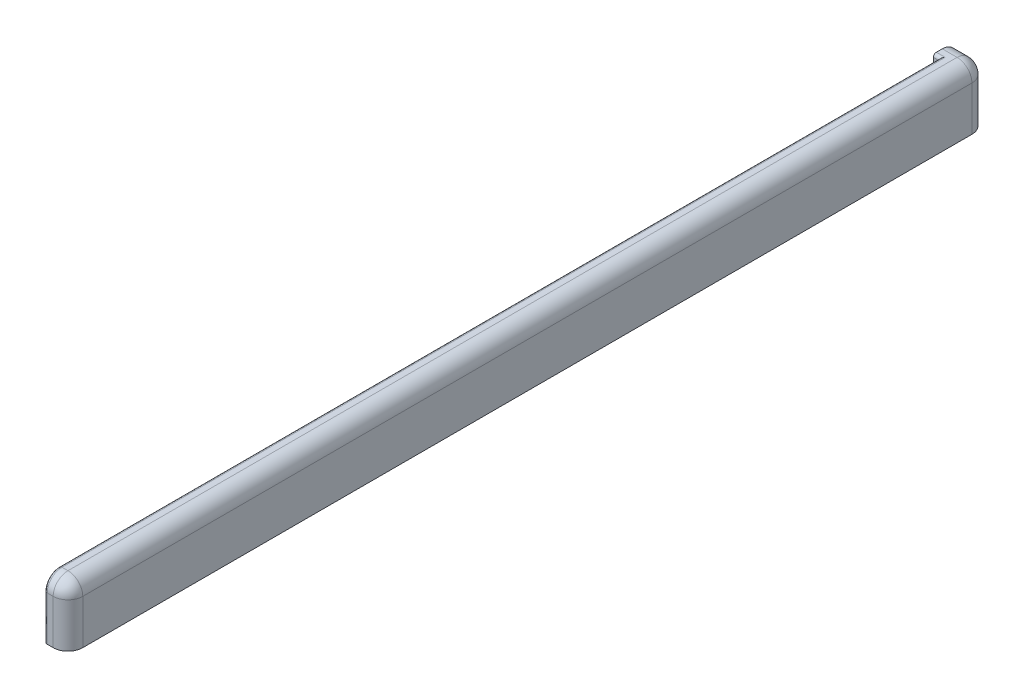
SolidWorks part; units mm, degrees
ref_plane "Front Plane" through (0, 0, 0) normal (0, 0, 1) x (1, 0, 0)
ref_plane "Top Plane" through (0, 0, 0) normal (0, 1, 0) x (1, 0, 0)
ref_plane "Right Plane" through (0, 0, 0) normal (1, 0, 0) x (0, 0, -1)
sketch "Sketch1" plane through (0, 0, 0) normal (0, 1, 0) x (1, 0, 0)
  line L1 (-19.5, 77.5) -> (19.5, 77.5)
  line L2 (-19.5, 77.5) -> (-19.5, -77.5)
  line L3 (-19.5, -77.5) -> (19.5, -77.5)
  line L4 (19.5, 77.5) -> (19.5, -77.5)
  line L5 (-19.5, 77.5) -> (19.5, -77.5) construction
  line L6 (-19.5, -77.5) -> (19.5, 77.5) construction
  point P0 (0, 0)
  dimension "D1" = 39
  dimension "D2" = 155
extrude "Boss-Extrude1" add sketch "Sketch1" along normal blind 2
sketch "Sketch2" plane through (0, 2, 0) normal (0, 1, 0) x (1, 0, 0)
  line L0 (-17.5, -75.5) -> (-17.5, -77.5)
  line L1 (-19.5, 77.5) -> (19.5, 77.5)
  line L2 (-19.5, 77.5) -> (-19.5, -77.5)
  line L3 (-19.5, -77.5) -> (19.5, -77.5)
  line L4 (19.5, 77.5) -> (19.5, -77.5)
  line L5 (-17.5, 75.5) -> (17.5, 75.5)
  line L6 (-17.5, 75.5) -> (-17.5, -75.5)
  line L7 (-17.5, -75.5) -> (17.5, -75.5)
  line L8 (17.5, 75.5) -> (17.5, -75.5)
  line L9 (-17.5, 75.5) -> (17.5, -75.5) construction
  line L10 (-17.5, -75.5) -> (17.5, 75.5) construction
  line L11 (17.5, -75.5) -> (17.5, -77.5)
  point P6 (0, 0)
  line M9 (19.5, -77.5) -> (19.5, 77.5)
  line M10 (19.5, 77.5) -> (-19.5, 77.5)
  line M11 (-19.5, 77.5) -> (-19.5, -77.5)
  line M12 (-19.5, -77.5) -> (19.5, -77.5)
  dimension "D1" = 2
  dimension "D2" = 2
extrude "Boss-Extrude2" add sketch "Sketch2" along normal blind 38 contours L8 L11 L3 L0 L6 L5 M9 M10 M11 M12 region at (-19.0983, 2, 76.5)
sketch "Sketch3" plane through (0, 2, 0) normal (0, 1, 0) x (1, 0, 0)
  line L0 (-17.5, 75.5) -> (-17.5, -77.5) construction
  line L1 (-17.5, -77.5) -> (-15.5, -77.5)
  line L2 (-17.5, -77.5) -> (-17.5, -75.5)
  line L3 (-17.5, -75.5) -> (-15.5, -75.5)
  line L4 (-15.5, -77.5) -> (-15.5, -75.5)
  line L5 (-17.5, -73.3) -> (-15.5, -73.3)
  line L6 (-17.5, -73.3) -> (-17.5, -71.3)
  line L7 (-17.5, -71.3) -> (-15.5, -71.3)
  line L8 (-15.5, -73.3) -> (-15.5, -71.3)
  line L9 (17.5, 75.5) -> (17.5, -77.5) construction
  line L10 (17.5, -77.5) -> (15.5, -77.5)
  line L11 (17.5, -77.5) -> (17.5, -75.5)
  line L12 (17.5, -75.5) -> (15.5, -75.5)
  line L13 (15.5, -77.5) -> (15.5, -75.5)
  line L14 (17.5, -73.3) -> (15.5, -73.3)
  line L15 (17.5, -73.3) -> (17.5, -71.3)
  line L16 (17.5, -71.3) -> (15.5, -71.3)
  line L17 (15.5, -73.3) -> (15.5, -71.3)
  line L18 (15.5, -75.5) -> (15.5, -73.3) construction
  line L19 (-15.5, -73.3) -> (15.5, -73.3) construction
  line L20 (-15.5, -75.5) -> (-15.5, -73.3) construction
  line L21 (-15.5, -75.5) -> (15.5, -75.5) construction
  line L22 (15.5, -71.3) -> (-15.5, -71.3) construction
  dimension "D1" = 2
  dimension "D2" = 2
  dimension "D3" = 2.2
  dimension "D4" = 2
extrude "Boss-Extrude3" add sketch "Sketch3" along normal up to surface (38 mm away) up to face at (0, 40, 0.5)
sketch "Sketch4" plane through (0, 0, -75.5) normal (0, 0, 1) x (1, 0, 0)
  line L0 (-17.5, 40) -> (-15.5, 40)
  line L1 (-17.5, 40) -> (17.5, 40) construction
  line L2 (-15.5, 40) -> (-15.5, 38)
  line L3 (-15.5, 38) -> (-17.5, 38)
  line L5 (-17.5, 38) -> (-17.5, 40)
  line L7 (-17.5, 40) -> (-17.5, 2) construction
  line L8 (-15.5, 33.8) -> (-17.5, 31.8)
  line L9 (-17.5, 31.8) -> (-17.5, 35.8)
  line L10 (-15.5, 33.8) -> (-15.5, 35.8)
  line L11 (-15.5, 35.8) -> (-17.5, 35.8)
  line L12 (0, 0) -> (0, 40) construction
  line L13 (15.5, 35.8) -> (17.5, 35.8)
  line L14 (15.5, 33.8) -> (15.5, 35.8)
  line L15 (17.5, 31.8) -> (17.5, 35.8)
  line L16 (15.5, 33.8) -> (17.5, 31.8)
  line L17 (17.5, 38) -> (17.5, 40)
  line L18 (15.5, 38) -> (17.5, 38)
  line L19 (15.5, 40) -> (15.5, 38)
  line L20 (17.5, 40) -> (15.5, 40)
  dimension "D1" = 2
  dimension "D2" = 2
  dimension "D3" = 45
  dimension "D4" = 2.2
  dimension "D5" = 2
extrude "Boss-Extrude4" add sketch "Sketch4" along normal up to surface (153 mm away) up to face at (0, 20.5, 77.5)
sketch "Sketch5" plane through (0, 2, 0) normal (0, 1, 0) x (1, 0, 0)
  line L1 (-15.5, -77.5) -> (15.5, -77.5)
  line L2 (-15.5, -77.5) -> (-15.5, -75.5)
  line L3 (-15.5, -75.5) -> (15.5, -75.5)
  line L4 (15.5, -77.5) -> (15.5, -75.5)
  line L5 (-15.5, -71.3) -> (15.5, -71.3)
  line L6 (-15.5, -71.3) -> (-15.5, -73.3)
  line L7 (-15.5, -73.3) -> (15.5, -73.3)
  line L8 (15.5, -71.3) -> (15.5, -73.3)
sketch "Sketch6" plane through (0, 0, -75.5) normal (0, 0, 1) x (1, 0, 0)
  line L0 (-17.5, 38) -> (-15.5, 38) construction
  line L1 (-17.5, 38) -> (17.5, 38)
  line L2 (-17.5, 38) -> (-17.5, 35.8)
  line L3 (-17.5, 35.8) -> (17.5, 35.8)
  line L4 (17.5, 38) -> (17.5, 35.8)
  line L5 (-17.5, 38) -> (-17.5, 35.8) construction
  line L6 (-15.5, 35.8) -> (-17.5, 35.8) construction
extrude "Cut-Extrude1" cut sketch "Sketch6" along normal through all
sketch "Sketch7" plane through (0, 2, 0) normal (0, 1, 0) x (1, 0, 0)
  line L1 (-17.5, -75.5) -> (17.5, -75.5)
  line L2 (-17.5, -75.5) -> (-17.5, -73.3)
  line L3 (-17.5, -73.3) -> (17.5, -73.3)
  line L4 (17.5, -75.5) -> (17.5, -73.3)
extrude "Cut-Extrude2" cut sketch "Sketch7" along normal through all
extrude "Boss-Extrude5" add sketch "Sketch5" along normal blind 2
sketch "Sketch8" plane through (0, 0, 0) normal (1, 0, 0) x (0, 0, -1)
  line L0 (75.5, 40) -> (73.5, 40)
  line L1 (-73.3, 40) -> (75.5, 40) construction
  line L2 (73.5, 40) -> (73.5, 38)
  line L3 (-73.3, 38) -> (75.5, 38) construction
  line L4 (73.5, 38) -> (75.5, 38)
  line L5 (75.5, 38) -> (75.5, 40)
  line L6 (75.5, 35.8) -> (73.5, 35.8)
  line L7 (-73.3, 35.8) -> (75.5, 35.8) construction
  line L8 (73.5, 35.8) -> (73.5, 33.8)
  line L9 (-71.3, 33.8) -> (75.5, 33.8) construction
  line L10 (73.5, 33.8) -> (75.5, 31.8)
  line L11 (75.5, 31.8) -> (75.5, 35.8)
  dimension "D1" = 2
extrude "Boss-Extrude6" add sketch "Sketch8" along normal up to surface and the other way up to surface up to face at (17.5, 16.9, -2.1) other way up to face at (-17.5, 16.9, -2.1)
sketch "Sketch10" plane through (-17.5, 0, 0) normal (1, 0, 0) x (0, 0, -1)
  line L1 (-75.5, 35.8) -> (-77.5, 35.8)
  line L2 (-75.5, 35.8) -> (-75.5, 38)
  line L3 (-75.5, 38) -> (-77.5, 38)
  line L4 (-77.5, 35.8) -> (-77.5, 38)
  line L5 (-73.3, 40) -> (-75.5, 40)
  line L6 (-73.3, 40) -> (-73.3, 38)
  line L7 (-73.3, 38) -> (-75.5, 38)
  line L8 (-75.5, 40) -> (-75.5, 38)
  line M1 (-75.5, 40) -> (-75.5, 38)
  line M2 (-75.5, 38) -> (-77.5, 38)
  line M3 (-77.5, 38) -> (-77.5, 35.8)
  line M4 (-77.5, 35.8) -> (-75.5, 35.8)
  line M11 (-73.3, 38) -> (-73.3, 40)
  line M12 (-73.3, 40) -> (-75.5, 40)
extrude "Boss-Extrude8" add sketch "Sketch10" along normal up to surface (2 mm away) contours L2 M4 M2 M3 | L7 M11 M12 M1 region at (-17.5, 39, 74.4) region at (-17.5, 36.9, 76.5) up to face at (-15.5, 39, -0.1)
sketch "Sketch11" plane through (17.5, 0, 0) normal (-1, 0, 0) x (0, 0, 1)
  line L1 (75.5, 35.8) -> (77.5, 35.8)
  line L2 (75.5, 35.8) -> (75.5, 38)
  line L3 (75.5, 38) -> (77.5, 38)
  line L4 (77.5, 35.8) -> (77.5, 38)
  line L5 (73.3, 40) -> (75.5, 40)
  line L6 (73.3, 40) -> (73.3, 38)
  line L7 (73.3, 38) -> (75.5, 38)
  line L8 (75.5, 40) -> (75.5, 38)
  line M2 (75.5, 35.8) -> (77.5, 35.8)
  line M3 (77.5, 35.8) -> (77.5, 38)
  line M4 (77.5, 38) -> (75.5, 38)
  line M5 (75.5, 38) -> (75.5, 40)
  line M6 (75.5, 40) -> (73.3, 40)
  line M7 (73.3, 40) -> (73.3, 38)
extrude "Boss-Extrude9" add sketch "Sketch11" along normal up to surface (2 mm away) contours L2 M2 M3 M4 | L7 M7 M5 M6 region at (17.5, 36.9, 76.5) region at (17.5, 39, 74.4) up to face at (15.5, 39, 76.5)
fillet "Fillet2" radius 2.5 17 edges at (-17.5, 16.9, 71.3) (17.5, 16.9, 71.3) (19.5, 20, 77.5) (-19.5, 20, 77.5) (-19.5, 20, -77.5) (-17.5, 16.9, -75.5) (17.5, 16.9, -75.5) (19.5, 20, -77.5) (-19.5, 40, 0) (0, 40, -77.5) (19.5, 40, 0) (0, 0, -77.5) (0, 0, 77.5) (-19.5, 0, 0) (19.5, 0, 0) (-17.5, 40, 77.5) (17.5, 40, 77.5)
sketch "Sketch13" plane through (0, 0, -77.5) normal (0, 0, -1) x (-1, 0, 0)
  line L0 (15.5, 37.5) -> (15.5, 4) construction
  line L1 (-15.5, 7) -> (15.5, 7)
  line L2 (-15.5, 7) -> (-15.5, 4)
  line L3 (-15.5, 4) -> (15.5, 4)
  line L4 (15.5, 7) -> (15.5, 4)
  dimension "D1" = 3
sketch "Sketch14" plane through (0, 0, -75.5) normal (0, 0, 1) x (1, 0, 0)
  line L1 (-18.25, 9) -> (18.25, 9)
  line L2 (-18.25, 9) -> (-18.25, 1.25)
  line L3 (-18.25, 1.25) -> (18.25, 1.25)
  line L4 (18.25, 9) -> (18.25, 1.25)
  line L5 (15.5, 7) -> (-15.5, 7) construction
  line L7 (17, 0) -> (17, 2.5) construction
  line L8 (19.5, 2.5) -> (17, 2.5) construction
  line L10 (-19.5, 2.5) -> (-17, 2.5) construction
  point P20 (17, 1.25)
  point P23 (18.25, 2.5)
  point P26 (-18.25, 2.5)
  dimension "D1" = 2
extrude "Boss-Extrude10" add sketch "Sketch14" along normal blind 2
extrude "Cut-Extrude4" cut sketch "Sketch13" against normal blind 2
fillet "Fillet3" radius 2 1 edges at (0, 9, -73.5)
fillet "Fillet4" radius 0.5 12 edges at (0, 4, -77.5) (0, 7, -77.5) (15.5, 7, -76.5) (15.5, 4, -76.5) (15.5, 5.5, -77.5) (-15.5, 4, -76.5) (-15.5, 7, -76.5) (-15.5, 5.5, -77.5) (0, 7, -75.5) (-15.5, 5.5, -75.5) (0, 4, -75.5) (15.5, 5.5, -75.5)
sketch "Sketch15" plane through (0, 0, 0) normal (0, -1, 0) x (1, 0, 0)
  line L0 (0, 77.5) -> (0, 0) construction
  line L1 (-17, 77.5) -> (17, 77.5) construction
  line L2 (0, 0) -> (0, -77.5) construction
  line L4 (17, -77.5) -> (-17, -77.5) construction
  circle A0 centre (0, 38.75) radius 5.1
  circle A1 centre (0, -38.75) radius 5.1
  dimension "D1" = 10.2
extrude "Cut-Extrude5" cut sketch "Sketch15" against normal through all
sketch "Sketch16" plane through (0, 2, 0) normal (0, 1, 0) x (1, 0, 0)
  circle A0 centre (0, 38.75) radius 7.1
  circle A1 centre (0, -38.75) radius 7.1
  circle A2 centre (0, 38.75) radius 5.1 construction
  dimension "D1" = 2
extrude "Boss-Extrude11" add sketch "Sketch16" along normal blind 1
fillet "Fillet5" radius 0.5 4 edges at (0, 2, 45.85) (0, 2, -31.65) (0, 3, 45.85) (0, 3, -31.65)
sketch "Sketch12" plane through (0, 0, -75.5) normal (0, 0, 1) x (1, 0, 0)
  line L0 (0, 0) -> (0, 40) construction
  line L1 (15.5, 40) -> (-15.5, 40) construction
  line L2 (0, 20) -> (-10, 20)
  line L3 (0, 20) -> (-9.0097, 15.6612)
  line L4 (0, 20) -> (-6.2349, 12.1817)
  line L5 (0, 20) -> (-2.2252, 10.2507)
  line L6 (0, 20) -> (2.2252, 10.2507)
  line L7 (0, 20) -> (6.2349, 12.1817)
  line L8 (0, 20) -> (9.0097, 15.6612)
  line L9 (0, 20) -> (10, 20)
  line L10 (0, 20) -> (9.0097, 24.3388)
  line L11 (0, 20) -> (6.2349, 27.8183)
  line L12 (0, 20) -> (2.2252, 29.7493)
  line L13 (0, 20) -> (-2.2252, 29.7493)
  line L14 (0, 20) -> (-6.2349, 27.8183)
  line L15 (0, 20) -> (-9.0097, 24.3388)
  circle A0 centre (0, 20) radius 10
  circle A1 centre (0, 20) radius 7.5
  circle A2 centre (0, 20) radius 5
  circle A3 centre (0, 20) radius 2.5
  point P26 (0, 20)
  dimension "D1" = 20
  dimension "D2" = 2.5
  dimension "D3" = 2.5
  dimension "D4" = 2.5
  dimension "D5" = 14
extrude "Cut-Extrude3" cut sketch "Sketch12" against normal through all contours A1 L6 A0 L7 | A1 L4 A0 L5 | A1 L2 A0 L3 | A1 L14 A0 L15 | A1 L0 A0 L13 | L0 A1 L12 A0 | A1 L10 A0 L11 | A1 L8 A0 L9 | A3 L8 A2 L9 | A3 L10 A2 L11 | L0 A3 L12 A2 | A3 L0 A2 L13 | A3 L14 A2 L15 | A3 L2 A2 L3 | A3 L4 A2 L5 | A3 L6 A2 L7 region at (-3.7903, 12.1293, -75.5) region at (3.7903, 12.1293, -75.5) region at (-1.6732, 16.5256, -75.5) region at (1.6732, 16.5256, -75.5) region at (-8.5168, 18.0561, -75.5) region at (8.5168, 18.0561, -75.5) region at (-0.4345, 23.8563, -75.5) region at (0.4345, 23.8563, -75.5) region at (-3.7596, 19.1419, -75.5) region at (3.7596, 19.1419, -75.5) region at (3.015, 22.4044, -75.5) region at (-3.015, 22.4044, -75.5) region at (-6.8299, 25.4467, -75.5) region at (6.8299, 25.4467, -75.5) region at (-0.9843, 28.7358, -75.5) region at (0.9843, 28.7358, -75.5)
fillet "Fillet6" radius 0.4 112 edges at (5.4555, 26.841, -77.5) (7.8183, 26.2349, -77.5) (7.8835, 23.7965, -77.5) (5.8637, 24.6762, -77.5) (3.75, 20, -77.5) (4.8746, 18.8874, -77.5) (3.3786, 18.3729, -77.5) (2.4373, 19.4437, -77.5) (-1.9471, 28.5306, -77.5) (0, 30, -77.5) (1.9471, 28.5306, -77.5) (0, 27.5, -77.5) (-7.8835, 16.2035, -77.5) (-9.7493, 17.7748, -77.5) (-8.75, 20, -77.5) (-7.312, 18.3311, -77.5) (2.3381, 17.0681, -77.5) (2.1694, 15.4952, -77.5) (0.8345, 16.344, -77.5) (1.0847, 17.7476, -77.5) (-0.8345, 16.344, -77.5) (-2.1694, 15.4952, -77.5) (-2.3381, 17.0681, -77.5) (-1.0847, 17.7476, -77.5) (5.4555, 13.159, -77.5) (4.3388, 10.9903, -77.5) (1.9471, 11.4694, -77.5) (3.2541, 13.2427, -77.5) (0, 22.5, -77.5) (-0.8345, 23.656, -77.5) (0, 25, -77.5) (0.8345, 23.656, -77.5) (-3.3786, 21.6271, -77.5) (-3.9092, 23.1174, -77.5) (-2.3381, 22.9319, -77.5) (-1.9546, 21.5587, -77.5) (-3.3786, 18.3729, -77.5) (-4.8746, 18.8874, -77.5) (-3.75, 20, -77.5) (-2.4373, 19.4437, -77.5) (-1.9471, 11.4694, -77.5) (-4.3388, 10.9903, -77.5) (-5.4555, 13.159, -77.5) (-3.2541, 13.2427, -77.5) (-7.8835, 23.7965, -77.5) (-7.8183, 26.2349, -77.5) (-5.4555, 26.841, -77.5) (-5.8637, 24.6762, -77.5) (2.3381, 22.9319, -77.5) (3.9092, 23.1174, -77.5) (3.3786, 21.6271, -77.5) (1.9546, 21.5587, -77.5) (8.75, 20, -77.5) (9.7493, 17.7748, -77.5) (7.8835, 16.2035, -77.5) (7.312, 18.3311, -77.5) (7.8835, 23.7965, -75.5) (7.8183, 26.2349, -75.5) (5.4555, 26.841, -75.5) (5.8637, 24.6762, -75.5) (3.3786, 18.3729, -75.5) (4.8746, 18.8874, -75.5) (3.75, 20, -75.5) (2.4373, 19.4437, -75.5) (1.9471, 28.5306, -75.5) (0, 30, -75.5) (-1.9471, 28.5306, -75.5) (0, 27.5, -75.5) (-8.75, 20, -75.5) (-9.7493, 17.7748, -75.5) (-7.8835, 16.2035, -75.5) (-7.312, 18.3311, -75.5) (0.8345, 16.344, -75.5) (2.1694, 15.4952, -75.5) (2.3381, 17.0681, -75.5) (1.0847, 17.7476, -75.5) (-2.3381, 17.0681, -75.5) (-2.1694, 15.4952, -75.5) (-0.8345, 16.344, -75.5) (-1.0847, 17.7476, -75.5) (1.9471, 11.4694, -75.5) (4.3388, 10.9903, -75.5) (5.4555, 13.159, -75.5) (3.2541, 13.2427, -75.5) (0, 22.5, -75.5) (0.8345, 23.656, -75.5) (0, 25, -75.5) (-0.8345, 23.656, -75.5) (-2.3381, 22.9319, -75.5) (-3.9092, 23.1174, -75.5) (-3.3786, 21.6271, -75.5) (-1.9546, 21.5587, -75.5) (-3.75, 20, -75.5) (-4.8746, 18.8874, -75.5) (-3.3786, 18.3729, -75.5) (-2.4373, 19.4437, -75.5) (-5.4555, 13.159, -75.5) (-4.3388, 10.9903, -75.5) (-1.9471, 11.4694, -75.5) (-3.2541, 13.2427, -75.5) (-5.4555, 26.841, -75.5) (-7.8183, 26.2349, -75.5) (-7.8835, 23.7965, -75.5) (-5.8637, 24.6762, -75.5) (3.3786, 21.6271, -75.5) (3.9092, 23.1174, -75.5) (2.3381, 22.9319, -75.5) (7.8835, 16.2035, -75.5) (9.7493, 17.7748, -75.5) (8.75, 20, -75.5) (7.312, 18.3311, -75.5) (1.9546, 21.5587, -75.5)
fillet "Fillet7" radius 0.5 8 edges at (15.5, 40, 0.75) (15.5, 39.2678, 76.7678) (-15.5, 40, 0.75) (-15.5, 39.2678, 76.7678) (0, 40, -73.5) (15.5, 20.75, 77.5) (-15.5, 20.75, 77.5) (0, 4, 77.5)
sketch "Sketch17" plane through (0, 0, 0) normal (0, -1, 0) x (1, 0, 0)
  line L0 (-17, -77.5) -> (-17, 70.3)
  line L1 (-17, -77.5) -> (17, -77.5)
  line L2 (17, -77.5) -> (17, 70.3)
  line L3 (17, -75) -> (17, 75) construction
  line L5 (17, 70.3) -> (15, 71.3)
  line L6 (15, 71.3) -> (15, 77.5)
  line L7 (15, 77.5) -> (-15, 77.5)
  line L8 (-15, 77.5) -> (-15, 71.3)
  line L9 (-15, 71.3) -> (-17, 70.3)
  line L10 (-17, 75) -> (-17, -75) construction
  line L12 (-15, 71.3) -> (15, 71.3) construction
  line L13 (17, 70.3) -> (-17, 70.3) construction
  line L14 (0, 71.3) -> (0, 77.5) construction
  line L15 (-17, 77.5) -> (17, 77.5) construction
  arc A0 (-19.5, -75) -> (-17, -77.5) centre (-17, -75) ccw construction
  dimension "D1" = 1
  dimension "D2" = 30
  dimension "D3" = 6.2
extrude "Cut-Extrude6" cut sketch "Sketch17" against normal blind 6
sketch "Sketch18" plane through (0, 0, 0) normal (0, 0, 1) x (1, 0, 0)
  line L0 (15, 9) -> (-15, 9) construction
  line L1 (-14.5, 9) -> (14.5, 9)
  line L2 (-14.5, 9) -> (-14.5, 6)
  line L3 (-14.5, 6) -> (14.5, 6)
  line L4 (14.5, 9) -> (14.5, 6)
  line L5 (-17, 6) -> (17, 6) construction
  line L6 (0, 6) -> (0, 0) construction
  dimension "D1" = 29
extrude "Cut-Extrude8" cut sketch "Sketch18" against normal through all
sketch "Sketch20" plane through (0, 0, 0) normal (0, 0, 1) x (1, 0, 0)
  line L0 (-16, 40) -> (16, 40) construction
  line L1 (-19.5, 40) -> (-14.5, 40)
  line L2 (-19.5, 40) -> (-19.5, 0)
  line L3 (-19.5, 0) -> (-14.5, 0)
  line L4 (-14.5, 40) -> (-14.5, 0)
  line L5 (-14.5, 6) -> (14.5, 6)
  line L6 (-14.5, 6) -> (-14.5, 40)
  line L7 (-14.5, 40) -> (14.5, 40)
  line L8 (14.5, 6) -> (14.5, 40)
  line L9 (14.5, 40) -> (19.5, 40)
  line L10 (14.5, 40) -> (14.5, 0)
  line L11 (14.5, 0) -> (19.5, 0)
  line L12 (19.5, 40) -> (19.5, 0)
  line L13 (-15, 0) -> (-17, 0) construction
  line L14 (-19.5, 2.5) -> (-19.5, 37.5) construction
  line L15 (17, 0) -> (15, 0) construction
  line L16 (19.5, 37.5) -> (19.5, 2.5) construction
extrude "Cut-Extrude11" cut sketch "Sketch20" against normal through all both and the other way through all contours L5 L8 L7 L4 | L1 L2 L3 L4 region at (0, 23, 0)
sketch "Sketch21" plane through (0, 0, 0) normal (1, 0, 0) x (0, 0, -1)
  line L1 (-77.5, 40) -> (77.5, 40)
  line L2 (-77.5, 40) -> (-77.5, 30)
  line L3 (-77.5, 30) -> (77.5, 30)
  line L4 (77.5, 40) -> (77.5, 30)
  line L5 (77.5, 30) -> (-77.5, 30)
  line L6 (77.5, 30) -> (77.5, 10)
  line L7 (77.5, 10) -> (-77.5, 10)
  line L8 (-77.5, 30) -> (-77.5, 10)
  line L9 (-77.5, 10) -> (77.5, 10)
  line L10 (-77.5, 10) -> (-77.5, 0)
  line L11 (-77.5, 0) -> (77.5, 0)
  line L12 (77.5, 10) -> (77.5, 0)
  line L16 (77.5, 30) -> (77.5, 10)
  line L17 (-77.5, 10) -> (-77.5, 30)
  line L18 (77.5, 37.5) -> (77.5, 6) construction
  line L19 (-75, 40) -> (75, 40) construction
  line L20 (-77.5, 2.5) -> (-77.5, 37.5) construction
  line L21 (75, 0) -> (-70.3, 0) construction
  dimension "D1" = 20
  dimension "D2" = 10
extrude "Cut-Extrude12" cut sketch "Sketch21" along normal through all contours L3 L8 L7 L6 | L12 L7 L10 L11 region at (0, 20, 0) region at (0, 5, 0)
